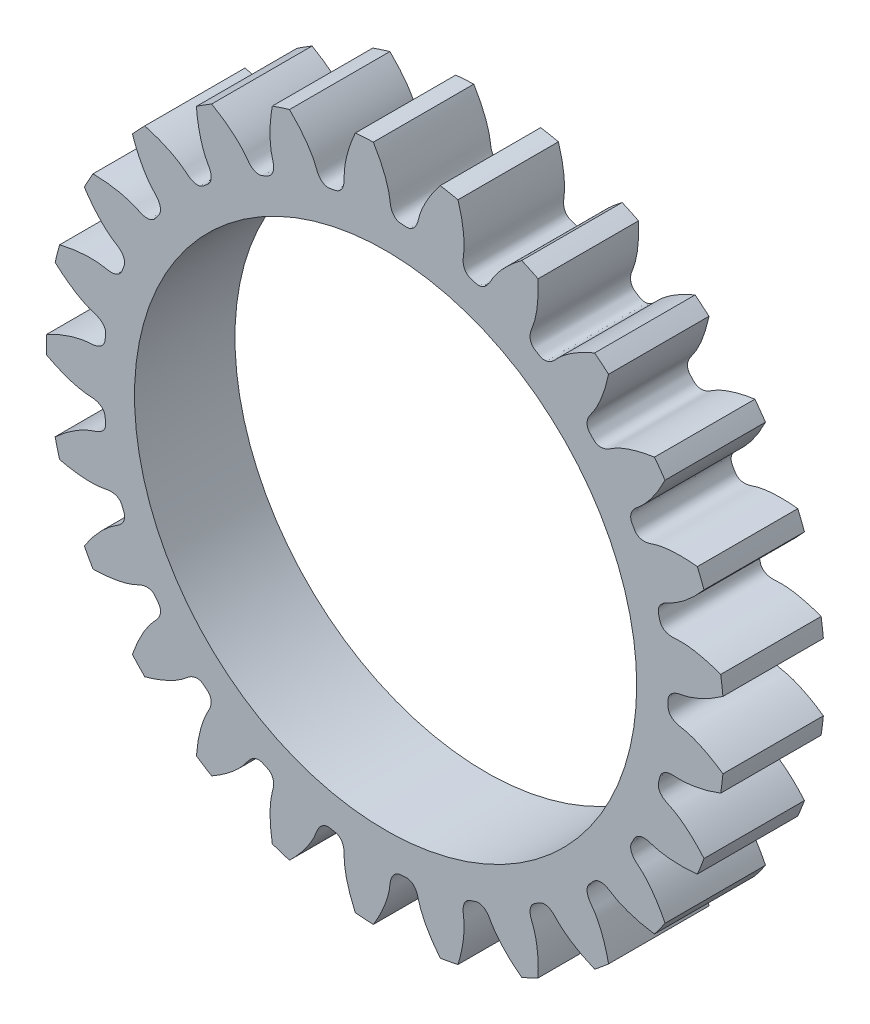
SolidWorks part; units mm, degrees
ref_plane "Front Plane" through (0, 0, 0) normal (0, 0, 1) x (1, 0, 0)
ref_plane "Top Plane" through (0, 0, 0) normal (0, 1, 0) x (1, 0, 0)
ref_plane "Right Plane" through (0, 0, 0) normal (1, 0, 0) x (0, 0, -1)
ref_axis "Axis1" through (0, 0, 55) along (0, 0, -1)
sketch "SketchRevolveSpurGear" plane through (0, 0, 0) normal (1, 0, 0) x (0, 0, -1)
  line L0 (0, 0) -> (1, 0) construction
  line L1 (-2, 0) -> (-2, 13.5)
  line L2 (-2, 13.5) -> (2, 13.5)
  line L3 (2, 13.5) -> (2, 0)
  line L4 (2, 0) -> (-2, 0)
  dimension "Side1" = 2
  dimension "OutsideRadius" = 13.5
  dimension "Side2" = 2
revolve "SpurGear" add sketch "SketchRevolveSpurGear" angle 360 about L0
sketch "SketchToothSpurGear" plane through (0, 0, 0) normal (0, 0, 1) x (1, 0, 0)
  arc A0 (13.4808, 1.3678) -> (13.4808, -1.3678) centre (0, 0) cw
  spline S0 degree 3 poles (13.4808, -1.3678) (13.3809, -1.296) (13.2321, -1.1951) (13.0336, -1.073) (12.8947, -0.993) (12.7622, -0.9216) (12.6363, -0.8584) (12.5175, -0.8029) (12.406, -0.7547) (12.3023, -0.7134) (12.2065, -0.6784) (12.119, -0.6492) (12.0399, -0.6253) (11.9696, -0.6063) (11.9082, -0.5915) (11.7994, -0.5687) (11.6917, -0.5539) (11.5891, -0.5202) (11.5399, -0.5007) (11.4922, -0.4777) (11.4458, -0.4502) (11.4003, -0.4167) (11.3558, -0.3752) (11.3139, -0.3228) (11.2778, -0.2573) (11.2557, -0.1838) (11.2468, -0.0962) (11.252, 0) (11.2468, 0.0962) (11.2557, 0.1838) (11.2778, 0.2573) (11.3139, 0.3228) (11.3558, 0.3752) (11.4003, 0.4167) (11.4458, 0.4502) (11.4922, 0.4777) (11.5399, 0.5007) (11.5891, 0.5202) (11.6917, 0.5539) (11.7994, 0.5687) (11.9082, 0.5915) (11.9696, 0.6063) (12.0399, 0.6253) (12.119, 0.6492) (12.2065, 0.6784) (12.3023, 0.7134) (12.406, 0.7547) (12.5175, 0.8029) (12.6363, 0.8584) (12.7622, 0.9216) (12.8947, 0.993) (13.0336, 1.073) (13.2321, 1.1951) (13.3809, 1.296) (13.4808, 1.3678) knots 0 0 0 0 0.066628 0.097312 0.126243 0.153421 0.178845 0.202515 0.224432 0.244596 0.263007 0.279664 0.294568 0.307718 0.319115 0.328758 0.367986 0.377666 0.387173 0.396652 0.406297 0.416368 0.427194 0.439149 0.45255 0.467442 0.48044 0.5 0.51956 0.532558 0.54745 0.560851 0.572806 0.583632 0.593703 0.603348 0.612827 0.622334 0.632014 0.671242 0.680885 0.692282 0.705432 0.720336 0.736993 0.755404 0.775568 0.797485 0.821155 0.846579 0.873757 0.902688 0.933372 1 1 1 1
extrude "ToothExtrudeCutSpurGear" cut sketch "SketchToothSpurGear" against normal blind 2 and the other way blind 2
pattern_circular "PatternSpurGear" count 25 every 14.4 about axis through (0, 0, 55) along (0, 0, -1) of "ToothExtrudeCutSpurGear"
sketch "BoreRevolveSketch" plane through (0, 0, 0) normal (1, 0, 0) x (0, 0, -1)
  line L0 (0, 0) -> (1, 0) construction
  line L1 (-2, 0) -> (2, 0)
  line L2 (2, 0) -> (2, 10)
  line L3 (2, 10) -> (-2, 10)
  line L4 (-2, 10) -> (-2, 0)
  dimension "BoreSide1" = 2
  dimension "TaperSide1" = 10
  dimension "BoreSide2" = 2
  dimension "TaperSide2" = 10
revolve "BoreRevolveCut" cut sketch "BoreRevolveSketch" angle 360 about L0
sketch "AuxiliarySketchSpurGear" plane through (0, 0, 0) normal (0, 0, 1) x (1, 0, 0)
  circle A0 centre (0, 0) radius 12.5 construction
  circle A1 centre (0, 0) radius 11.7462 construction
  circle A2 centre (0, 0) radius 11.8071 construction
  circle A3 centre (0, 0) radius 13.5 construction
  circle A4 centre (0, 0) radius 11.25 construction
  dimension "PitchDiameter" = 25
  dimension "BaseDiameter" = 23.4923
  dimension "FormDiameter" = 23.6141
  dimension "MajorDiameter" = 27
  dimension "MinorDiameter" = 22.5
